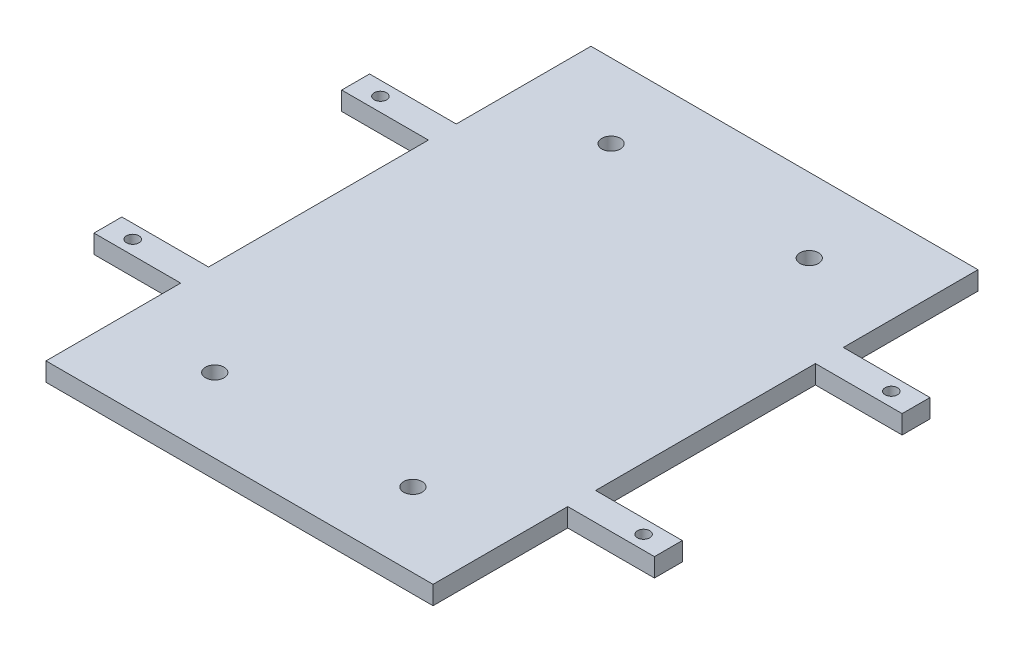
SolidWorks part; units mm, degrees
ref_plane "Front Plane" through (0, 0, 0) normal (0, 0, 1) x (1, 0, 0)
ref_plane "Top Plane" through (0, 0, 0) normal (0, 1, 0) x (1, 0, 0)
ref_plane "Right Plane" through (0, 0, 0) normal (1, 0, 0) x (0, 0, -1)
sketch "Sketch1" plane through (0, 0, 0) normal (0, 1, 0) x (1, 0, 0)
  line L0 (0, 0) -> (-31.25, 0) construction
  line L1 (-31.25, -44) -> (31.25, -44) construction
  line L2 (-31.25, -44) -> (-31.25, 17.75) construction
  line L3 (-31.25, 44) -> (31.25, 44) construction
  line L4 (31.25, -44) -> (31.25, 44) construction
  line L5 (-31.25, -44) -> (31.25, 44) construction
  line L6 (-31.25, 44) -> (31.25, -44) construction
  line L7 (-45.25, 22.25) -> (-31.25, 22.25)
  line L8 (-45.25, 22.25) -> (-45.25, 17.75)
  line L9 (-45.25, 17.75) -> (-31.25, 17.75)
  line L11 (-45.25, 22.25) -> (-31.25, 17.75) construction
  line L12 (-45.25, 17.75) -> (-31.25, 22.25) construction
  line L13 (-31.25, 22.25) -> (-31.25, 44) construction
  line L14 (-45.25, -17.75) -> (-31.25, -17.75)
  line L15 (-45.25, -22.25) -> (-45.25, -17.75)
  line L16 (-45.25, -22.25) -> (-31.25, -22.25)
  line L17 (0, 0) -> (0, 44) construction
  line L18 (-31.25, -17.75) -> (-31.25, 17.75)
  line L19 (31.25, 44) -> (-31.25, 44)
  line L20 (-31.25, 44) -> (-31.25, 22.25)
  line L21 (-31.25, -44) -> (-31.25, -22.25)
  line L22 (31.25, -44) -> (-31.25, -44)
  line L23 (31.25, -44) -> (31.25, -22.25)
  line L24 (45.25, -22.25) -> (31.25, -22.25)
  line L25 (45.25, -22.25) -> (45.25, -17.75)
  line L26 (45.25, -17.75) -> (31.25, -17.75)
  line L27 (31.25, -17.75) -> (31.25, 17.75)
  line L28 (45.25, 17.75) -> (31.25, 17.75)
  line L29 (45.25, 22.25) -> (45.25, 17.75)
  line L30 (45.25, 22.25) -> (31.25, 22.25)
  line L31 (31.25, 44) -> (31.25, 22.25)
  point P0 (0, 0)
  point P6 (-38.25, 20)
  point P19 (0, -44)
  dimension "D1" = 62.5
  dimension "D2" = 88
  dimension "D3" = 14
  dimension "D4" = 4.5
  dimension "D5" = 20
extrude "Boss-Extrude1" add sketch "Sketch1" along normal blind 3
sketch "Sketch2" plane through (0, 0, 0) normal (0, -1, 0) x (1, 0, 0)
  line L0 (-45.25, 17.75) -> (-45.25, 22.25) construction
  line L1 (-31.25, 22.25) -> (-31.25, 44) construction
  line L2 (0, 0) -> (-31.25, 0) construction
  line L3 (-31.25, -17.75) -> (-31.25, 17.75) construction
  line L4 (0, 0) -> (0, 44) construction
  line L5 (-31.25, 44) -> (31.25, 44) construction
  circle A0 centre (-41.25, 20) radius 1
  circle A1 centre (-41.25, -20) radius 1
  circle A2 centre (41.25, -20) radius 1
  circle A3 centre (41.25, 20) radius 1
  point P5 (-45.25, 20)
  point P12 (0, 0)
  dimension "D2" = 2
  dimension "D1" = 10
extrude "Cut-Extrude1" cut sketch "Sketch2" against normal blind 6
sketch "Sketch3" plane through (0, 3, 0) normal (0, 1, 0) x (1, 0, 0)
  line L1 (16, -32) -> (-16, -32) construction
  line L2 (16, -32) -> (16, 32) construction
  line L3 (16, 32) -> (-16, 32) construction
  line L4 (-16, -32) -> (-16, 32) construction
  line L5 (16, -32) -> (-16, 32) construction
  line L6 (16, 32) -> (-16, -32) construction
  circle A0 centre (-16, 32) radius 1.5
  circle A1 centre (16, 32) radius 1.5
  circle A2 centre (16, -32) radius 1.5
  circle A3 centre (-16, -32) radius 1.5
  point P0 (0, 0)
  dimension "D3" = 3
  dimension "D1" = 32
  dimension "D2" = 64
extrude "Cut-Extrude2" cut sketch "Sketch3" against normal blind 10
